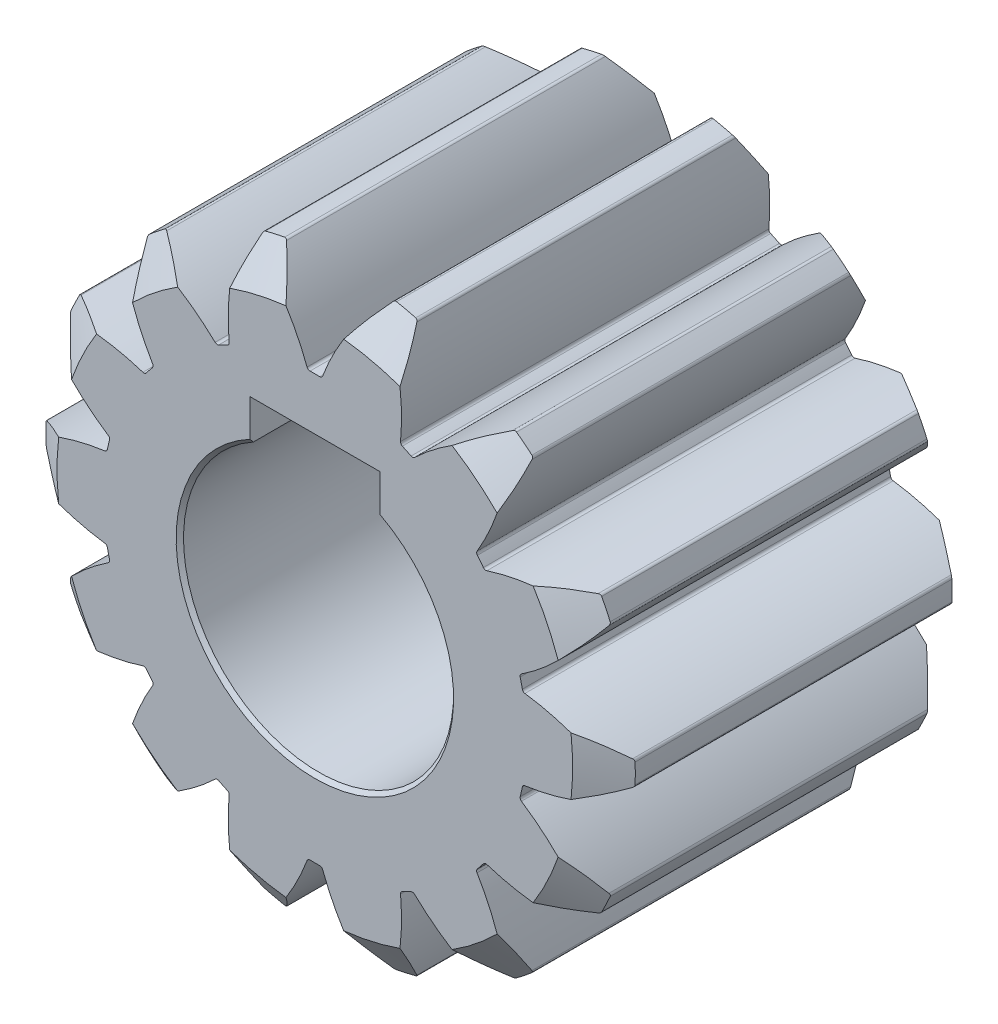
SolidWorks part; units mm, degrees
ref_plane "前视基准面" through (0, 0, 0) normal (0, 0, 1) x (1, 0, 0)
ref_plane "上视基准面" through (0, 0, 0) normal (0, 1, 0) x (1, 0, 0)
ref_plane "右视基准面" through (0, 0, 0) normal (1, 0, 0) x (0, 0, -1)
sketch "草图1" plane through (0, 0, 0) normal (1, 0, 0) x (0, 0, -1)
  line L0 (0, 0) -> (15, 0) construction
  line L1 (0, 3.5) -> (15, 3.5)
  line L4 (15, 3.5) -> (15, 12)
  line L5 (15, 12) -> (0, 12)
  line L6 (0, 12) -> (0, 3.5)
  line L7 (0, 0) -> (-1.5, 0) construction
  line L8 (-1.5, 0) -> (-1.5, -14) construction
  line L9 (15, 0) -> (15, -3)
  line L10 (15, -3) -> (16.4, -3)
  dimension "P" = 7
  dimension "B" = 15
  dimension "M" = 1.5
  dimension "Z" = 14
  dimension "D" = 24
  dimension "b_" = 3
  dimension "t_" = 1.4
sketch "草图11" plane through (-11.8785, -4, 0) normal (0, 0, 1) x (1, 0, 0)
  line L0 (11.8785, 4) -> (23.8785, 4) construction
  line L1 (22.3125, 2.8244) -> (11.8785, 4) construction
  circle A0 centre (11.8785, 4) radius 8.625
  arc A1 (20.3463, 2.3607) -> (20.5035, 4) centre (11.8785, 4) ccw construction
  arc A2 (22.3125, 2.8244) -> (22.3785, 4) centre (11.8785, 4) ccw construction
  arc A3 (23.8692, 3.5289) -> (23.8692, 4.4711) centre (11.8785, 4) ccw construction
  arc A4 (20.3463, 2.3607) -> (23.8692, 3.5289) centre (19.125, 11.9401) ccw construction
  point P1 (25.8785, 4)
  point P7 (11.8785, 5.5)
  point P13 (22.3125, 2.8244)
  point P17 (23.8692, 4.4711)
  point P18 (20.3463, 5.6393)
  dimension "D1" = 24
  dimension "D" = 21
  dimension "D2" = 17.25
  dimension "m" = 1.5
  dimension "z" = 14
  dimension "D3" = 6.429
  dimension "D4" = 0.9425
  dimension "D5" = 3.2987
extrude "拉伸-齿轮a" add sketch "草图11" against normal blind 15
sketch "草图3" plane through (-1.3611, -4, 0) normal (0, 0, 1) x (1, 0, 0)
  line L1 (1.3611, 4) -> (13.3611, 4) construction
  line L2 (9.9861, 4) -> (13.3611, 4) construction
  circle A2 centre (1.3611, 4) radius 8.625 construction
  arc A3 (9.8288, 2.3607) -> (13.3518, 3.5289) centre (8.6076, 11.9401) ccw construction
  arc A4 (13.3518, 3.5289) -> (13.3518, 4.4711) centre (1.3611, 4) ccw construction
  arc A5 (9.8288, 2.3607) -> (9.8288, 5.6393) centre (1.3611, 4) ccw
  arc A6 (9.8288, 2.3607) -> (13.3518, 3.5289) centre (8.6076, 11.9401) ccw
  arc A7 (13.3518, 3.5289) -> (13.3518, 4.4711) centre (1.3611, 4) ccw
  arc A8 (9.8288, 5.6393) -> (13.3518, 4.4711) centre (8.6076, -3.9401) cw
extrude "拉伸-齿轮b" add sketch "草图3" along normal up to surface (-15 mm away) up to face at (8.625, 0, -15)
fillet "圆角-齿轮" radius 0.125 4 edges at (11.9907, -0.4711, -7.5) (11.9907, 0.4711, -7.5) (8.4678, -1.6393, -7.5) (8.4678, 1.6393, -7.5)
pattern_circular "阵列-齿轮" count 14 over 360 about axis through (0, 0, -15) along (0, 0, 1) of "拉伸-齿轮b", "圆角-齿轮"
sketch "草图4" plane through (0, 0, -15) normal (0, 0, -1) x (-1, 0, 0)
  line L0 (-10.5, 0) -> (-13.5, 0) construction
  circle A0 centre (0, 0) radius 13.5
  circle A1 centre (0, 0) radius 10.5
extrude "切除-齿轮" cut sketch "草图4" against normal blind 1.5 draft 55
extrude "切除-拉伸2" cut sketch "草图4<2>" along normal blind 1.5 draft 55 from vertex starting at point (0, 3.5, 0)
sketch "草图4<2>" plane through (0, 0, -15) normal (0, 0, -1) x (-1, 0, 0) same geometry as "草图4"
sketch "草图13" plane through (0, 0, 0) normal (0, 0, 1) x (1, 0, 0)
  circle A0 centre (0, 0) radius 5.5
  dimension "D1" = 11
extrude "切除-拉伸4" cut sketch "草图13" against normal through all
chamfer "倒角1" distance 0.15 angle 45 2 edges at (5.5, 0, 0) (5.5, 0, -15)
sketch "草图14" plane through (0, 0, -15) normal (0, 0, -1) x (-1, 0, 0)
  line L1 (-2.65, 6.5) -> (2.65, 6.5)
  line L2 (-2.65, 6.5) -> (-2.65, 3.5)
  line L3 (-2.65, 3.5) -> (2.65, 3.5)
  line L4 (2.65, 6.5) -> (2.65, 3.5)
  line L5 (-2.65, 6.5) -> (2.65, 3.5) construction
  line L6 (-2.65, 3.5) -> (2.65, 6.5) construction
  circle A1 centre (0, 0) radius 5.5 construction
  point P0 (0, 0)
  point P1 (0, 5)
  point P9 (0, 0)
  dimension "D1" = 5.3
  dimension "D2" = 3
  dimension "D3" = 6.5
extrude "键槽孔型" cut sketch "草图14" against normal through all
